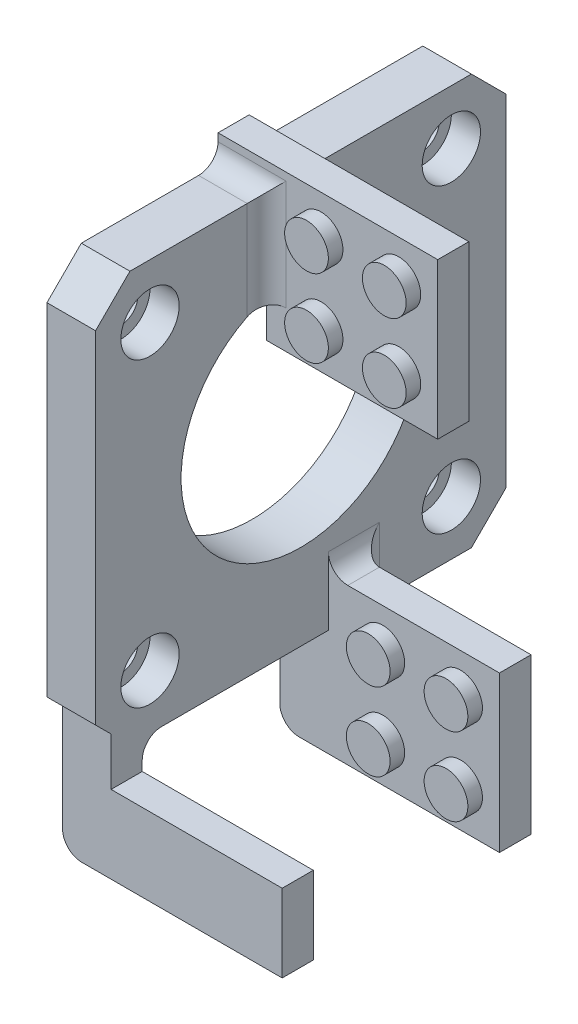
SolidWorks part; units mm, degrees
ref_plane "Front Plane" through (0, 0, 0) normal (0, 0, 1) x (1, 0, 0)
ref_plane "Top Plane" through (0, 0, 0) normal (0, 1, 0) x (1, 0, 0)
ref_plane "Right Plane" through (0, 0, 0) normal (1, 0, 0) x (0, 0, -1)
sketch "Sketch4" plane through (-14.6, 0, 0) normal (1, 0, 0) x (0, 0, -1)
  line L2 (11.2546, -49.194) -> (11.2546, 22.806) construction
  line L4 (-1.5454, -49.194) -> (-1.5454, -33.194) construction
  line L5 (17.6046, -33.194) -> (17.6046, -49.194) construction
  line L6 (11.2546, -49.194) -> (11.2546, 22.806) construction
  line L7 (11.2546, -49.194) -> (11.2546, 22.806) construction
  line L8 (-6.3454, 0.4704) -> (-6.3454, -34.6585)
  line L9 (-6.3454, -34.6585) -> (-2.8099, -38.194)
  line L10 (-2.8099, -38.194) -> (32.3191, -38.194)
  line L11 (32.3191, -38.194) -> (35.8546, -34.6585)
  line L12 (35.8546, -34.6585) -> (35.8546, 0.4704)
  line L13 (35.8546, 0.4704) -> (32.3191, 4.006)
  line L14 (32.3191, 4.006) -> (-2.8099, 4.006)
  line L15 (-2.8099, 4.006) -> (-6.3454, 0.4704)
  line L16 (-6.3454, 0.4704) -> (-6.3454, -34.6585)
  line L17 (-6.3454, -34.6585) -> (-2.8099, -38.194)
  line L18 (-2.8099, -38.194) -> (32.3191, -38.194)
  line L19 (32.3191, -38.194) -> (35.8546, -34.6585)
  line L20 (35.8546, -34.6585) -> (35.8546, 0.4704)
  line L21 (35.8546, 0.4704) -> (32.3191, 4.006)
  line L22 (32.3191, 4.006) -> (-2.8099, 4.006)
  line L23 (-2.8099, 4.006) -> (-6.3454, 0.4704)
  line L24 (-1.5454, -49.194) -> (-1.5454, -33.194) construction
  line L25 (17.6046, -33.194) -> (17.6046, -49.194) construction
  line L26 (11.2546, -47.594) -> (11.2546, -42.794) construction
  line L27 (11.2546, -39.594) -> (11.2546, -34.794) construction
  line L28 (11.2546, 0.406) -> (11.2546, 5.206) construction
  line L29 (11.2546, -7.594) -> (11.2546, -2.794) construction
  line L30 (11.2546, -47.594) -> (11.2546, -42.794) construction
  line L31 (11.2546, -39.594) -> (11.2546, -34.794) construction
  line L32 (11.2546, 0.406) -> (11.2546, 5.206) construction
  line L33 (11.2546, -7.594) -> (11.2546, -2.794) construction
  line L34 (-1.5454, -38.194) -> (-1.5454, -49.194)
  line L35 (20.8546, -49.194) -> (17.6046, -49.194)
  line L36 (20.8546, -49.194) -> (20.8546, -33.194)
  line L37 (20.8546, -33.194) -> (17.6046, -33.194)
  line L38 (17.6046, -49.194) -> (17.6046, -33.194)
  line L39 (20.8546, -49.194) -> (17.6046, -33.194) construction
  line L40 (20.8546, -33.194) -> (17.6046, -49.194) construction
  line L41 (-1.5454, -49.194) -> (-4.7454, -49.194)
  line L42 (-4.7454, -49.194) -> (-4.7454, -36.2585)
  line L43 (11.2546, -41.194) -> (-4.7454, -41.194)
  line L44 (11.2546, -9.194) -> (14.4546, -9.194)
  line L45 (14.4546, -9.194) -> (14.4546, 6.806)
  line L46 (14.4546, 6.806) -> (11.2546, 6.806)
  line L47 (11.2546, 6.806) -> (11.2546, -9.194)
  line L48 (11.2546, -2.794) -> (11.2546, 0.406) construction
  line L49 (11.2546, -2.794) -> (11.2546, 0.406)
  circle A0 centre (14.7546, -17.094) radius 12.3
  circle A1 centre (14.7546, -17.094) radius 12
  circle A2 centre (14.7546, -17.094) radius 12 construction
  arc A3 (30.2546, -0.334) -> (29.2407, -0.8459) centre (30.2546, -1.594) ccw
  arc A4 (31.2685, -0.8459) -> (30.2546, -0.334) centre (30.2546, -1.594) ccw
  arc A5 (29.6767, -2.9891) -> (30.8324, -2.9891) centre (30.2546, -1.594) ccw
  arc A6 (30.2546, -0.334) -> (29.2407, -0.8459) centre (30.2546, -1.594) ccw construction
  arc A7 (31.2685, -0.8459) -> (30.2546, -0.334) centre (30.2546, -1.594) ccw construction
  arc A8 (29.6767, -2.9891) -> (30.8324, -2.9891) centre (30.2546, -1.594) ccw construction
  arc A9 (30.2546, -31.334) -> (29.2407, -31.8459) centre (30.2546, -32.594) ccw
  arc A10 (31.2685, -31.8459) -> (30.2546, -31.334) centre (30.2546, -32.594) ccw
  arc A11 (29.6767, -33.9891) -> (30.8324, -33.9891) centre (30.2546, -32.594) ccw
  arc A12 (30.2546, -31.334) -> (29.2407, -31.8459) centre (30.2546, -32.594) ccw construction
  arc A13 (31.2685, -31.8459) -> (30.2546, -31.334) centre (30.2546, -32.594) ccw construction
  arc A14 (29.6767, -33.9891) -> (30.8324, -33.9891) centre (30.2546, -32.594) ccw construction
  arc A15 (-0.7454, -0.334) -> (-1.7593, -0.8459) centre (-0.7454, -1.594) ccw
  arc A16 (0.2685, -0.8459) -> (-0.7454, -0.334) centre (-0.7454, -1.594) ccw
  arc A17 (-1.3233, -2.9891) -> (-0.1676, -2.9891) centre (-0.7454, -1.594) ccw
  arc A18 (-0.7454, -0.334) -> (-1.7593, -0.8459) centre (-0.7454, -1.594) ccw construction
  arc A19 (0.2685, -0.8459) -> (-0.7454, -0.334) centre (-0.7454, -1.594) ccw construction
  arc A20 (-1.3233, -2.9891) -> (-0.1676, -2.9891) centre (-0.7454, -1.594) ccw construction
  arc A21 (-0.7454, -31.334) -> (-1.7593, -31.8459) centre (-0.7454, -32.594) ccw
  arc A22 (0.2685, -31.8459) -> (-0.7454, -31.334) centre (-0.7454, -32.594) ccw
  arc A23 (-1.3233, -33.9891) -> (-0.1676, -33.9891) centre (-0.7454, -32.594) ccw
  arc A24 (-0.7454, -31.334) -> (-1.7593, -31.8459) centre (-0.7454, -32.594) ccw construction
  arc A25 (0.2685, -31.8459) -> (-0.7454, -31.334) centre (-0.7454, -32.594) ccw construction
  arc A26 (-1.3233, -33.9891) -> (-0.1676, -33.9891) centre (-0.7454, -32.594) ccw construction
  circle A27 centre (-0.7454, -32.594) radius 1.75
  circle A28 centre (-0.7454, -32.594) radius 3
  circle A29 centre (-0.7454, -1.594) radius 1.75
  circle A30 centre (-0.7454, -1.594) radius 3
  circle A31 centre (30.2546, -1.594) radius 1.75
  circle A32 centre (30.2546, -1.594) radius 3
  circle A33 centre (30.2546, -32.594) radius 1.75
  circle A34 centre (30.2546, -32.594) radius 3
  spline S2 degree 6 poles (1416.109, -1445.2831) (36.5495, 19.5258) (42.2492, 9.3255) (23.5656, 4.5699) (26.025, -3.8798) (30.1217, -4.2099) (31.4012, -2.4681) (31.4587, -2.3722) (31.507, -2.2715) (31.5454, -2.1669) (31.5736, -2.0598) (31.6095, -1.8395) (31.6167, -1.7262) (31.6125, -1.6129) (31.5971, -1.501) (31.5705, -1.3919) (30.9149, 0.4612) (27.361, 1.0487) (23.2159, -6.052) (40.0913, -18.1944) (65.1794, -26.2102) (1503.4217, 1352.3912) knots -4.213254 -4.213254 -4.213254 -4.213254 -4.213254 -4.213254 -4.213254 0.240234 0.240234 0.240234 0.240234 0.240234 0.482752 0.482752 0.482752 0.482752 0.482752 0.732681 0.732681 0.732681 0.732681 0.732681 4.898115 4.898115 4.898115 4.898115 4.898115 4.898115 4.898115 weights 1 1 1 1 1 1 1 1 1 1 1 1 1 1 1 1 1 1 1 1 1 1 only from (30.8324, -2.9891) to (31.2685, -0.8459)
  spline S3 degree 6 poles (-1441.994, 1353.3548) (-4.7582, -26.2184) (20.4368, -18.1909) (37.2912, -6.0484) (33.147, 1.0485) (29.5942, 0.4609) (28.9387, -1.3919) (28.9121, -1.501) (28.8966, -1.6129) (28.8925, -1.7262) (28.8996, -1.8395) (28.9356, -2.0598) (28.9638, -2.1669) (29.0022, -2.2715) (29.0504, -2.3722) (29.108, -2.4681) (30.3875, -4.2099) (34.4842, -3.8798) (36.9436, 4.57) (18.2592, 9.3243) (23.9798, 19.5389) (-1355.77, -1445.1389) knots -3.897393 -3.897393 -3.897393 -3.897393 -3.897393 -3.897393 -3.897393 0.267319 0.267319 0.267319 0.267319 0.267319 0.517248 0.517248 0.517248 0.517248 0.517248 0.759766 0.759766 0.759766 0.759766 0.759766 5.213238 5.213238 5.213238 5.213238 5.213238 5.213238 5.213238 weights 1 1 1 1 1 1 1 1 1 1 1 1 1 1 1 1 1 1 1 1 1 1 only from (29.2407, -0.8459) to (29.6767, -2.9891)
  spline S4 degree 6 poles (30.8324, -2.9891) (30.9316, -2.937) (31.0259, -2.8761) (31.1143, -2.8071) (31.1958, -2.7305) (31.2697, -2.6471) (31.4012, -2.4681) (31.4587, -2.3722) (31.507, -2.2715) (31.5454, -2.1669) (31.5736, -2.0598) (31.6095, -1.8395) (31.6167, -1.7262) (31.6125, -1.6129) (31.5971, -1.501) (31.5705, -1.3919) (31.5044, -1.205) (31.4689, -1.1255) (31.4272, -1.0492) (31.3796, -0.9769) (31.3265, -0.9089) (31.2685, -0.8459) knots 0 0 0 0 0 0 0 0.240234 0.240234 0.240234 0.240234 0.240234 0.482752 0.482752 0.482752 0.482752 0.482752 0.732681 0.732681 0.732681 0.732681 0.732681 0.928164 0.928164 0.928164 0.928164 0.928164 0.928164 0.928164 weights 1 1 1 1 1 1 1 1 1 1 1 1 1 1 1 1 1 1 1 1 1 1 construction
  spline S5 degree 6 poles (29.2407, -0.8459) (29.1827, -0.9089) (29.1296, -0.9768) (29.082, -1.0492) (29.0403, -1.1255) (29.0048, -1.205) (28.9387, -1.3919) (28.9121, -1.501) (28.8966, -1.6129) (28.8925, -1.7262) (28.8996, -1.8395) (28.9356, -2.0598) (28.9638, -2.1669) (29.0022, -2.2715) (29.0504, -2.3722) (29.108, -2.4681) (29.2395, -2.6471) (29.3134, -2.7305) (29.3949, -2.8071) (29.4833, -2.8761) (29.5776, -2.937) (29.6767, -2.9891) knots 0.071831 0.071831 0.071831 0.071831 0.071831 0.071831 0.071831 0.267319 0.267319 0.267319 0.267319 0.267319 0.517248 0.517248 0.517248 0.517248 0.517248 0.759766 0.759766 0.759766 0.759766 0.759766 1 1 1 1 1 1 1 weights 1 1 1 1 1 1 1 1 1 1 1 1 1 1 1 1 1 1 1 1 1 1 construction
  spline S6 degree 6 poles (1416.109, -1476.2819) (36.5495, -11.4742) (42.2492, -21.6745) (23.5656, -26.4301) (26.025, -34.8798) (30.1217, -35.2099) (31.4012, -33.4681) (31.4587, -33.3722) (31.507, -33.2715) (31.5454, -33.1669) (31.5736, -33.0598) (31.6095, -32.8395) (31.6167, -32.7262) (31.6125, -32.6129) (31.5971, -32.501) (31.5705, -32.3919) (30.9149, -30.5388) (27.361, -29.9513) (23.2159, -37.052) (40.0913, -49.1944) (65.1794, -57.2102) (1503.4217, 1321.3909) knots -4.213254 -4.213254 -4.213254 -4.213254 -4.213254 -4.213254 -4.213254 0.240234 0.240234 0.240234 0.240234 0.240234 0.482752 0.482752 0.482752 0.482752 0.482752 0.732681 0.732681 0.732681 0.732681 0.732681 4.898115 4.898115 4.898115 4.898115 4.898115 4.898115 4.898115 weights 1 1 1 1 1 1 1 1 1 1 1 1 1 1 1 1 1 1 1 1 1 1 only from (30.8324, -33.9891) to (31.2685, -31.8459)
  spline S7 degree 6 poles (-1441.994, 1322.3549) (-4.7582, -57.2183) (20.4368, -49.1909) (37.2912, -37.0484) (33.147, -29.9515) (29.5942, -30.5391) (28.9387, -32.3919) (28.9121, -32.501) (28.8966, -32.6129) (28.8925, -32.7262) (28.8996, -32.8395) (28.9356, -33.0598) (28.9638, -33.1669) (29.0022, -33.2715) (29.0504, -33.3722) (29.108, -33.4681) (30.3875, -35.2099) (34.4842, -34.8798) (36.9436, -26.43) (18.2592, -21.6757) (23.9798, -11.4613) (-1355.77, -1476.1345) knots -3.897393 -3.897393 -3.897393 -3.897393 -3.897393 -3.897393 -3.897393 0.267319 0.267319 0.267319 0.267319 0.267319 0.517248 0.517248 0.517248 0.517248 0.517248 0.759766 0.759766 0.759766 0.759766 0.759766 5.213238 5.213238 5.213238 5.213238 5.213238 5.213238 5.213238 weights 1 1 1 1 1 1 1 1 1 1 1 1 1 1 1 1 1 1 1 1 1 1 only from (29.2407, -31.8459) to (29.6767, -33.9891)
  spline S8 degree 6 poles (30.8324, -33.9891) (30.9316, -33.937) (31.0259, -33.8761) (31.1143, -33.8071) (31.1958, -33.7305) (31.2697, -33.6471) (31.4012, -33.4681) (31.4587, -33.3722) (31.507, -33.2715) (31.5454, -33.1669) (31.5736, -33.0598) (31.6095, -32.8395) (31.6167, -32.7262) (31.6125, -32.6129) (31.5971, -32.501) (31.5705, -32.3919) (31.5044, -32.205) (31.4689, -32.1255) (31.4272, -32.0492) (31.3796, -31.9769) (31.3265, -31.9089) (31.2685, -31.8459) knots 0 0 0 0 0 0 0 0.240234 0.240234 0.240234 0.240234 0.240234 0.482752 0.482752 0.482752 0.482752 0.482752 0.732681 0.732681 0.732681 0.732681 0.732681 0.928164 0.928164 0.928164 0.928164 0.928164 0.928164 0.928164 weights 1 1 1 1 1 1 1 1 1 1 1 1 1 1 1 1 1 1 1 1 1 1 construction
  spline S9 degree 6 poles (29.2407, -31.8459) (29.1827, -31.9089) (29.1296, -31.9768) (29.082, -32.0492) (29.0403, -32.1255) (29.0048, -32.205) (28.9387, -32.3919) (28.9121, -32.501) (28.8966, -32.6129) (28.8925, -32.7262) (28.8996, -32.8395) (28.9356, -33.0598) (28.9638, -33.1669) (29.0022, -33.2715) (29.0504, -33.3722) (29.108, -33.4681) (29.2395, -33.6471) (29.3134, -33.7305) (29.3949, -33.8071) (29.4833, -33.8761) (29.5776, -33.937) (29.6767, -33.9891) knots 0.071831 0.071831 0.071831 0.071831 0.071831 0.071831 0.071831 0.267319 0.267319 0.267319 0.267319 0.267319 0.517248 0.517248 0.517248 0.517248 0.517248 0.759766 0.759766 0.759766 0.759766 0.759766 1 1 1 1 1 1 1 weights 1 1 1 1 1 1 1 1 1 1 1 1 1 1 1 1 1 1 1 1 1 1 construction
  spline S10 degree 6 poles (1385.0993, -1445.2713) (5.5496, 19.5258) (11.2491, 9.3255) (-7.4344, 4.5699) (-4.975, -3.8798) (-0.8783, -4.2099) (0.4012, -2.4681) (0.4587, -2.3722) (0.507, -2.2715) (0.5454, -2.1669) (0.5736, -2.0598) (0.6095, -1.8395) (0.6167, -1.7262) (0.6125, -1.6129) (0.5971, -1.501) (0.5705, -1.3919) (-0.0851, 0.4612) (-3.639, 1.0487) (-7.784, -6.0519) (9.0909, -18.1941) (34.1787, -26.21) (1472.3697, 1352.3412) knots -4.213248 -4.213248 -4.213248 -4.213248 -4.213248 -4.213248 -4.213248 0.240234 0.240234 0.240234 0.240234 0.240234 0.482752 0.482752 0.482752 0.482752 0.482752 0.732681 0.732681 0.732681 0.732681 0.732681 4.89809 4.89809 4.89809 4.89809 4.89809 4.89809 4.89809 weights 1 1 1 1 1 1 1 1 1 1 1 1 1 1 1 1 1 1 1 1 1 1 only from (-0.1676, -2.9891) to (0.2685, -0.8459)
  spline S11 degree 6 poles (-1472.9924, 1353.3551) (-35.7582, -26.2184) (-10.5632, -18.1909) (6.2912, -6.0484) (2.147, 1.0485) (-1.4058, 0.4609) (-2.0613, -1.3919) (-2.0879, -1.501) (-2.1034, -1.6129) (-2.1075, -1.7262) (-2.1004, -1.8395) (-2.0644, -2.0598) (-2.0362, -2.1669) (-1.9978, -2.2715) (-1.9496, -2.3722) (-1.892, -2.4681) (-0.6125, -4.2099) (3.4842, -3.8798) (5.9436, 4.57) (-12.7408, 9.3243) (-7.0201, 19.5389) (-1386.7727, -1445.1389) knots -3.897393 -3.897393 -3.897393 -3.897393 -3.897393 -3.897393 -3.897393 0.267319 0.267319 0.267319 0.267319 0.267319 0.517248 0.517248 0.517248 0.517248 0.517248 0.759766 0.759766 0.759766 0.759766 0.759766 5.213238 5.213238 5.213238 5.213238 5.213238 5.213238 5.213238 weights 1 1 1 1 1 1 1 1 1 1 1 1 1 1 1 1 1 1 1 1 1 1 only from (-1.7593, -0.8459) to (-1.3233, -2.9891)
  spline S12 degree 6 poles (-0.1676, -2.9891) (-0.0684, -2.937) (0.0259, -2.8761) (0.1143, -2.8071) (0.1958, -2.7305) (0.2697, -2.6471) (0.4012, -2.4681) (0.4587, -2.3722) (0.507, -2.2715) (0.5454, -2.1669) (0.5736, -2.0598) (0.6095, -1.8395) (0.6167, -1.7262) (0.6125, -1.6129) (0.5971, -1.501) (0.5705, -1.3919) (0.5044, -1.205) (0.4689, -1.1255) (0.4272, -1.0492) (0.3796, -0.9769) (0.3265, -0.9089) (0.2685, -0.8459) knots 0 0 0 0 0 0 0 0.240234 0.240234 0.240234 0.240234 0.240234 0.482752 0.482752 0.482752 0.482752 0.482752 0.732681 0.732681 0.732681 0.732681 0.732681 0.928164 0.928164 0.928164 0.928164 0.928164 0.928164 0.928164 weights 1 1 1 1 1 1 1 1 1 1 1 1 1 1 1 1 1 1 1 1 1 1 construction
  spline S13 degree 6 poles (-1.7593, -0.8459) (-1.8173, -0.9089) (-1.8704, -0.9768) (-1.918, -1.0492) (-1.9597, -1.1255) (-1.9952, -1.205) (-2.0613, -1.3919) (-2.0879, -1.501) (-2.1034, -1.6129) (-2.1075, -1.7262) (-2.1004, -1.8395) (-2.0644, -2.0598) (-2.0362, -2.1669) (-1.9978, -2.2715) (-1.9496, -2.3722) (-1.892, -2.4681) (-1.7605, -2.6471) (-1.6866, -2.7305) (-1.6051, -2.8071) (-1.5167, -2.8761) (-1.4224, -2.937) (-1.3233, -2.9891) knots 0.071831 0.071831 0.071831 0.071831 0.071831 0.071831 0.071831 0.267319 0.267319 0.267319 0.267319 0.267319 0.517248 0.517248 0.517248 0.517248 0.517248 0.759766 0.759766 0.759766 0.759766 0.759766 1 1 1 1 1 1 1 weights 1 1 1 1 1 1 1 1 1 1 1 1 1 1 1 1 1 1 1 1 1 1 construction
  spline S14 degree 6 poles (1385.0999, -1476.27) (5.5495, -11.4743) (11.2491, -21.6745) (-7.4344, -26.4301) (-4.975, -34.8798) (-0.8783, -35.2099) (0.4012, -33.4681) (0.4587, -33.3722) (0.507, -33.2715) (0.5454, -33.1669) (0.5736, -33.0598) (0.6095, -32.8395) (0.6167, -32.7262) (0.6125, -32.6129) (0.5971, -32.501) (0.5705, -32.3919) (-0.0851, -30.5388) (-3.639, -29.9513) (-7.784, -37.0519) (9.0909, -49.1941) (34.1787, -57.21) (1472.3697, 1321.341) knots -4.213248 -4.213248 -4.213248 -4.213248 -4.213248 -4.213248 -4.213248 0.240234 0.240234 0.240234 0.240234 0.240234 0.482752 0.482752 0.482752 0.482752 0.482752 0.732681 0.732681 0.732681 0.732681 0.732681 4.89809 4.89809 4.89809 4.89809 4.89809 4.89809 4.89809 weights 1 1 1 1 1 1 1 1 1 1 1 1 1 1 1 1 1 1 1 1 1 1 only from (-0.1676, -33.9891) to (0.2685, -31.8459)
  spline S15 degree 6 poles (-1472.9924, 1322.3549) (-35.7582, -57.2183) (-10.5632, -49.1909) (6.2912, -37.0484) (2.147, -29.9515) (-1.4058, -30.5391) (-2.0613, -32.3919) (-2.0879, -32.501) (-2.1034, -32.6129) (-2.1075, -32.7262) (-2.1004, -32.8395) (-2.0644, -33.0598) (-2.0362, -33.1669) (-1.9978, -33.2715) (-1.9496, -33.3722) (-1.892, -33.4681) (-0.6125, -35.2099) (3.4842, -34.8798) (5.9436, -26.43) (-12.7408, -21.6757) (-7.0201, -11.4613) (-1386.7727, -1476.1345) knots -3.897393 -3.897393 -3.897393 -3.897393 -3.897393 -3.897393 -3.897393 0.267319 0.267319 0.267319 0.267319 0.267319 0.517248 0.517248 0.517248 0.517248 0.517248 0.759766 0.759766 0.759766 0.759766 0.759766 5.213238 5.213238 5.213238 5.213238 5.213238 5.213238 5.213238 weights 1 1 1 1 1 1 1 1 1 1 1 1 1 1 1 1 1 1 1 1 1 1 only from (-1.7593, -31.8459) to (-1.3233, -33.9891)
  spline S16 degree 6 poles (-0.1676, -33.9891) (-0.0684, -33.937) (0.0259, -33.8761) (0.1143, -33.8071) (0.1958, -33.7305) (0.2697, -33.6471) (0.4012, -33.4681) (0.4587, -33.3722) (0.507, -33.2715) (0.5454, -33.1669) (0.5736, -33.0598) (0.6095, -32.8395) (0.6167, -32.7262) (0.6125, -32.6129) (0.5971, -32.501) (0.5705, -32.3919) (0.5044, -32.205) (0.4689, -32.1255) (0.4272, -32.0492) (0.3796, -31.9769) (0.3265, -31.9089) (0.2685, -31.8459) knots 0 0 0 0 0 0 0 0.240234 0.240234 0.240234 0.240234 0.240234 0.482752 0.482752 0.482752 0.482752 0.482752 0.732681 0.732681 0.732681 0.732681 0.732681 0.928164 0.928164 0.928164 0.928164 0.928164 0.928164 0.928164 weights 1 1 1 1 1 1 1 1 1 1 1 1 1 1 1 1 1 1 1 1 1 1 construction
  spline S17 degree 6 poles (-1.7593, -31.8459) (-1.8173, -31.9089) (-1.8704, -31.9768) (-1.918, -32.0492) (-1.9597, -32.1255) (-1.9952, -32.205) (-2.0613, -32.3919) (-2.0879, -32.501) (-2.1034, -32.6129) (-2.1075, -32.7262) (-2.1004, -32.8395) (-2.0644, -33.0598) (-2.0362, -33.1669) (-1.9978, -33.2715) (-1.9496, -33.3722) (-1.892, -33.4681) (-1.7605, -33.6471) (-1.6866, -33.7305) (-1.6051, -33.8071) (-1.5167, -33.8761) (-1.4224, -33.937) (-1.3233, -33.9891) knots 0.071831 0.071831 0.071831 0.071831 0.071831 0.071831 0.071831 0.267319 0.267319 0.267319 0.267319 0.267319 0.517248 0.517248 0.517248 0.517248 0.517248 0.759766 0.759766 0.759766 0.759766 0.759766 1 1 1 1 1 1 1 weights 1 1 1 1 1 1 1 1 1 1 1 1 1 1 1 1 1 1 1 1 1 1 construction
  point P67 (19.2296, -41.194)
  point P81 (11.2546, -1.194)
  point P82 (14.4546, -1.194)
  dimension "D8" = 6
  dimension "D9" = 3.5
  dimension "D12" = 3.2
  dimension "D10" = 9.6
  dimension "D11" = 3.2
  dimension "D13" = 16
  dimension "D14" = 3.2
  dimension "D1" = 0
  dimension "D2" = 0
  dimension "D3" = 0
  dimension "D4" = 0
  dimension "D5" = 0
  dimension "D6" = 0
  dimension "D7" = 0.3
extrude "Boss-Extrude1" add sketch "Sketch4" along normal blind 5 contours A0 L47 L17 L18 L38 L37 L36 L45 A34 A32 A30 A28 | A34 A33 | A28 A27 | A30 A29 | A32 A31 | L46 L47 L22 L45 | L34 L43 L42 L41 | L38 L35 L36 | L43 L34 L17 L42 | L38 L36 L37 | A0 L45 L22 L47 region at (-14.6, 1.8162, 4.1556) region at (-14.6, -39.3438, 3.3013) region at (-14.6, 5.406, -12.8546) region at (-14.6, -0.4871, -12.8397) region at (-14.6, -45.194, 3.1454) region at (-14.6, -35.694, -19.2296) region at (-14.6, -43.694, -19.2296) region at (-14.6, -32.594, 3.6606) region at (-14.6, -1.594, 3.6606) region at (-14.6, -1.594, -27.3394) region at (-14.6, -32.594, -27.3394)
extrude "Boss-Extrude2" add sketch "Sketch4<3>" along normal up to surface (17.6 mm away) from surface contours L38 L35 L36 | L38 L36 L37 | L34 L43 L42 L41 | A0 L45 L22 L47 | L47 L44 L45 | L45 A0 L47 | L46 L47 L22 L45 region at (-14.6, 5.406, -12.8546) region at (-14.6, -0.4871, -12.8397) region at (-14.6, -45.194, 3.1454) region at (-14.6, -5.132, -12.8432) region at (-14.6, -35.694, -19.2296) region at (-14.6, -43.694, -19.2296) region at (-14.6, -7.2353, -12.8898) starting at face at (-9.6, -22.3448, -12.4527)
sketch "Sketch4<3>" plane through (-14.6, 0, 0) normal (1, 0, 0) x (0, 0, -1) same geometry as "Sketch4"
sketch "Sketch5" plane through (0, 0, -17.6046) normal (0, 0, 1) x (1, 0, 0)
  circle A0 centre (-4, -5.194) radius 2.4 construction
  circle A1 centre (4, -5.194) radius 2.4 construction
  circle A2 centre (4, 2.806) radius 2.4 construction
  circle A3 centre (-4, 2.806) radius 2.4 construction
  circle A4 centre (4, -45.194) radius 2.4 construction
  circle A5 centre (-4, -45.194) radius 2.4 construction
  circle A6 centre (-4, -37.194) radius 2.4 construction
  circle A7 centre (4, -37.194) radius 2.4 construction
  circle A8 centre (-4, -5.194) radius 2.4 construction
  circle A9 centre (4, -5.194) radius 2.4 construction
  circle A10 centre (4, 2.806) radius 2.4 construction
  circle A11 centre (-4, 2.806) radius 2.4 construction
  circle A12 centre (4, -45.194) radius 2.4 construction
  circle A13 centre (-4, -45.194) radius 2.4 construction
  circle A14 centre (-4, -37.194) radius 2.4 construction
  circle A15 centre (4, -37.194) radius 2.4 construction
  circle A16 centre (-4, -45.194) radius 2.55
  circle A17 centre (-4, -45.194) radius 2.25
  circle A18 centre (4, -45.194) radius 2.25
  circle A19 centre (4, -45.194) radius 2.55
  circle A20 centre (-4, -37.194) radius 2.25
  circle A21 centre (4, -37.194) radius 2.25
  circle A22 centre (-4, 2.806) radius 2.25
  circle A23 centre (4, 2.806) radius 2.25
  circle A24 centre (4, -5.194) radius 2.25
  circle A25 centre (-4, -5.194) radius 2.25
  dimension "D1" = 0.15
  dimension "D2" = 0.15
extrude "Boss-Extrude3" add sketch "Sketch5" along normal blind 1.5 contours A17 | A18 | A21 | A20 region at (-4, -45.194, -17.6046) region at (4, -45.194, -17.6046) region at (-4, -37.194, -17.6046) region at (4, -37.194, -17.6046)
extrude "Boss-Extrude4" add sketch "Sketch5<4>" along normal blind 1.5 from surface contours A22 | A25 | A23 | A24 region at (-4, 2.806, -17.6046) region at (4, 2.806, -17.6046) region at (4, -5.194, -17.6046) region at (-4, -5.194, -17.6046) starting at face at (-6, -0.2953, -11.2546)
sketch "Sketch5<4>" plane through (0, 0, -17.6046) normal (0, 0, 1) x (1, 0, 0) same geometry as "Sketch5"
extrude "Cut-Extrude1" cut sketch "Sketch5<5>" along normal blind 1.7 from surface contours A19 | A16 starting at face at (-5.4, -42.8607, 1.5454)
sketch "Sketch5<5>" plane through (0, 0, -17.6046) normal (0, 0, 1) x (1, 0, 0) same geometry as "Sketch5"
fillet "Fillet1" radius 2 10 edges at (-12.1, -38.194, 1.5454) (-12.1, 4.006, -11.2546) (-9.6, -0.6483, -11.2546) (-14.6, -49.194, 3.1454) (-14.6, -49.194, -19.2296) (-9.6, -33.194, -19.2296) (-12.1, -38.194, -20.8546) (-9.6, -35.694, -20.8546) (-12.1, 4.006, -14.4546) (-9.6, -0.3959, -14.4546)
extrude "Cut-Extrude2" cut sketch "Sketch4<4>" against normal blind 3 from surface contours A28 A27 | A30 A29 | A32 A31 | A34 A33 region at (-14.6, -32.594, 3.6606) region at (-14.6, -1.594, 3.6606) region at (-14.6, -1.594, -27.3394) region at (-14.6, -32.594, -27.3394) starting at face at (-9.6, -30.844, 0.7454)
sketch "Sketch4<4>" plane through (-14.6, 0, 0) normal (1, 0, 0) x (0, 0, -1) same geometry as "Sketch4"
